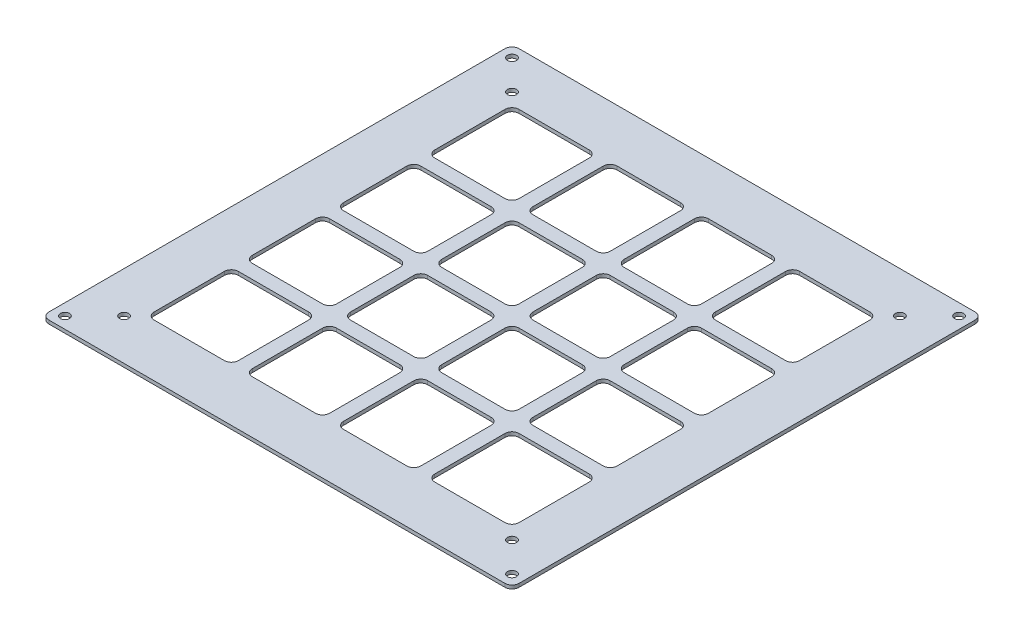
SolidWorks part; units mm, degrees
material "PC High Viscosity"
ref_plane "Front Plane" through (0, 0, 0) normal (0, 0, 1) x (1, 0, 0)
ref_plane "Top Plane" through (0, 0, 0) normal (0, 1, 0) x (1, 0, 0)
ref_plane "Right Plane" through (0, 0, 0) normal (1, 0, 0) x (0, 0, -1)
sketch "Sketch1" plane through (0, 0, 0) normal (0, 1, 0) x (1, 0, 0)
  line L0 (-101.8092, 0) -> (101.8092, 0) construction
  line L1 (-101.8092, 101.8092) -> (101.8092, 101.8092) construction
  line L2 (-101.8092, 101.8092) -> (-101.8092, -101.8092) construction
  line L3 (-101.8092, -101.8092) -> (101.8092, -101.8092) construction
  line L4 (101.8092, 101.8092) -> (101.8092, -101.8092) construction
  line L5 (-101.8092, 101.8092) -> (101.8092, -101.8092) construction
  line L6 (-101.8092, -101.8092) -> (101.8092, 101.8092) construction
  line L7 (-107.0543, 107.0543) -> (107.0543, 107.0543)
  line L8 (107.0543, 107.0543) -> (107.0543, -107.0543)
  line L9 (107.0543, -107.0543) -> (-107.0543, -107.0543)
  line L10 (-107.0543, -107.0543) -> (-107.0543, 107.0543)
  circle A0 centre (-101.8092, 101.8092) radius 2.0701
  circle A1 centre (-101.8092, -101.8092) radius 2.0701
  circle A2 centre (101.8092, -101.8092) radius 2.0701
  circle A3 centre (101.8092, 101.8092) radius 2.0701
  circle A4 centre (-88.3388, 88.3388) radius 2.0701
  circle A5 centre (88.3388, -88.3388) radius 2.0701
  circle A6 centre (88.3388, 88.3388) radius 2.0701
  circle A7 centre (-88.3388, -88.3388) radius 2.0701
  circle A8 centre (-101.8092, 101.8092) radius 5.2451 construction
  circle A9 centre (101.8092, 101.8092) radius 5.2451 construction
  circle A10 centre (101.8092, -101.8092) radius 5.2451 construction
  circle A11 centre (-101.8092, -101.8092) radius 5.2451 construction
  point P0 (0, 0)
  point P30 (0, 0)
  dimension "D2" = 4.1402
  dimension "D4" = 3.175
  dimension "D1" = 203.6183
  dimension "D3" = 19.05
  dimension "D5" = 4
extrude "Boss-Extrude1" add sketch "Sketch1" along normal blind 1.5875
sketch "Sketch2" plane through (0, 1.5875, 0) normal (0, 1, 0) x (1, 0, 0)
  line L0 (-50000, 0) -> (50000, 0) construction
  line L1 (0, 50000) -> (0, -50000) construction
  line L2 (0, 0) -> (-83.0937, 0) construction
  line L3 (0, 0) -> (0, 83.0937) construction
  line L4 (-83.0937, 83.0937) -> (-83.0937, -83.0937)
  line L5 (83.0937, 83.0937) -> (83.0937, -83.0937)
  line L6 (83.0937, -83.0937) -> (-83.0937, -83.0937)
  line L7 (-83.0937, 83.0937) -> (83.0937, 83.0937)
  line L8 (-41.5468, -83.0937) -> (-41.5468, 83.0937) construction
  line L9 (83.0937, 41.5468) -> (-83.0937, 41.5468) construction
  line L10 (83.0937, -41.5468) -> (-83.0937, -41.5468) construction
  line L11 (41.5468, -83.0937) -> (41.5468, 83.0937) construction
  line L12 (-83.0937, -3.175) -> (50000, -3.175)
  line L13 (-38.3718, -83.0937) -> (-38.3718, 83.0937)
  line L14 (83.0937, 44.7218) -> (-83.0937, 44.7218)
  line L15 (83.0937, -38.3718) -> (-83.0937, -38.3718)
  line L16 (-3.175, 83.0937) -> (-3.175, -83.0937)
  line L17 (44.7218, -83.0937) -> (44.7218, 83.0937)
  line L18 (-83.0937, 3.175) -> (50000, 3.175)
  line L19 (-44.7218, -83.0937) -> (-44.7218, 83.0937)
  line L20 (83.0937, 38.3718) -> (-83.0937, 38.3718)
  line L21 (83.0937, -44.7218) -> (-83.0937, -44.7218)
  line L22 (3.175, 83.0937) -> (3.175, -83.0937)
  line L23 (38.3718, -83.0937) -> (38.3718, 83.0937)
  line L24 (0, 44.7218) -> (-50000, 44.7218) construction
  line L25 (0, 41.5468) -> (-50000, 41.5468) construction
  line L26 (0, 38.3718) -> (-50000, 38.3718) construction
  line L27 (-50000, 3.175) -> (50000, 3.175) construction
  line L28 (-50000, -3.175) -> (50000, -3.175) construction
  line L29 (0, -38.3718) -> (-50000, -38.3718) construction
  line L30 (0, -41.5468) -> (-50000, -41.5468) construction
  line L31 (0, -44.7218) -> (-50000, -44.7218) construction
  line L32 (44.7218, 0) -> (44.7218, 50000) construction
  line L33 (41.5468, 0) -> (41.5468, 50000) construction
  line L34 (38.3718, 0) -> (38.3718, 50000) construction
  line L35 (-38.3718, 0) -> (-38.3718, 50000) construction
  line L36 (-41.5468, 0) -> (-41.5468, 50000) construction
  line L37 (-44.7218, 0) -> (-44.7218, 50000) construction
  line L38 (-3.175, 50000) -> (-3.175, -50000) construction
  line L39 (3.175, 50000) -> (3.175, -50000) construction
  circle A0 centre (-88.3388, 88.3388) radius 5.2451 construction
  circle A1 centre (-88.3388, 88.3388) radius 2.0701 construction
  circle A2 centre (88.3388, 88.3388) radius 5.2451 construction
  circle A3 centre (88.3388, -88.3388) radius 5.2451 construction
  circle A4 centre (-88.3388, -88.3388) radius 5.2451 construction
  point P19 (0, 0)
  point P22 (-41.5468, 0)
  point P27 (0, 41.5468)
  dimension "D1" = 3.175
  dimension "D3" = 3.175
  dimension "D4" = 3.175
  dimension "D2" = 4
extrude "Cut-Extrude1" cut sketch "Sketch2" against normal through all contours L14 L19 L7 L4 | L19 L20 L4 L18 | L16 L7 L13 L14 | L16 L20 L13 L18 | L14 L23 L7 L22 | L18 L23 L20 L22 | L17 L14 L5 L7 | L5 L20 L17 L18 | L17 L15 L5 L12 | L15 L23 L12 L22 | L16 L12 L13 L15 | L15 L19 L12 L4 | L19 L21 L4 L6 | L16 L21 L13 L6 | L6 L23 L21 L22 | L5 L21 L17 L6 region at (-63.9078, 1.5875, -63.9078) region at (-63.9078, 1.5875, -20.7734) region at (-20.7734, 1.5875, -63.9078) region at (-63.9078, 1.5875, 20.7734) region at (-20.7734, 1.5875, -20.7734) region at (20.7734, 1.5875, -63.9078) region at (-63.9078, 1.5875, 63.9078) region at (-20.7734, 1.5875, 20.7734) region at (20.7734, 1.5875, -20.7734) region at (63.9078, 1.5875, -63.9078) region at (-20.7734, 1.5875, 63.9078) region at (20.7734, 1.5875, 20.7734) region at (63.9078, 1.5875, -20.7734) region at (20.7734, 1.5875, 63.9078) region at (63.9078, 1.5875, 20.7734) region at (63.9078, 1.5875, 63.9078)
fillet "Fillet1" radius 3.175 4 edges at (-107.0543, 0.7937, 107.0543) (107.0543, 0.7937, 107.0543) (107.0543, 0.7937, -107.0543) (-107.0543, 0.7937, -107.0543)
fillet "Fillet2" radius 3.175 64 edges at (-38.3718, 0.7937, -44.7218) (-38.3718, 0.7937, -83.0937) (-3.175, 0.7937, -83.0937) (-3.175, 0.7937, -44.7218) (-38.3718, 0.7937, -3.175) (-38.3718, 0.7937, -38.3718) (-3.175, 0.7937, -38.3718) (-3.175, 0.7937, -3.175) (3.175, 0.7937, -83.0937) (38.3718, 0.7937, -83.0937) (38.3718, 0.7937, -44.7218) (3.175, 0.7937, -44.7218) (83.0937, 0.7937, -83.0937) (83.0937, 0.7937, -44.7218) (44.7218, 0.7937, -44.7218) (44.7218, 0.7937, -83.0937) (44.7218, 0.7937, -3.175) (44.7218, 0.7937, -38.3718) (83.0937, 0.7937, -38.3718) (83.0937, 0.7937, -3.175) (83.0937, 0.7937, 3.175) (83.0937, 0.7937, 38.3718) (44.7218, 0.7937, 38.3718) (44.7218, 0.7937, 3.175) (3.175, 0.7937, 3.175) (38.3718, 0.7937, 3.175) (38.3718, 0.7937, 38.3718) (3.175, 0.7937, 38.3718) (-38.3718, 0.7937, 38.3718) (-38.3718, 0.7937, 3.175) (-3.175, 0.7937, 3.175) (-3.175, 0.7937, 38.3718) (-83.0937, 0.7937, 3.175) (-44.7218, 0.7937, 3.175) (-44.7218, 0.7937, 38.3718) (-83.0937, 0.7937, 38.3718) (-38.3718, 0.7937, 83.0937) (-38.3718, 0.7937, 44.7218) (-3.175, 0.7937, 44.7218) (-3.175, 0.7937, 83.0937) (3.175, 0.7937, 44.7218) (38.3718, 0.7937, 44.7218) (38.3718, 0.7937, 83.0937) (3.175, 0.7937, 83.0937) (44.7218, 0.7937, 83.0937) (44.7218, 0.7937, 44.7218) (83.0937, 0.7937, 44.7218) (83.0937, 0.7937, 83.0937) (-83.0937, 0.7937, -83.0937) (-44.7218, 0.7937, -83.0937) (-44.7218, 0.7937, -44.7218) (-83.0937, 0.7937, -44.7218) (-44.7218, 0.7937, 83.0937) (-83.0937, 0.7937, 44.7218) (-44.7218, 0.7937, 44.7218) (3.175, 0.7937, -3.175) (3.175, 0.7937, -38.3718) (38.3718, 0.7937, -38.3718) (38.3718, 0.7937, -3.175) (-44.7218, 0.7937, -3.175) (-83.0937, 0.7937, -3.175) (-83.0937, 0.7937, -38.3718) (-44.7218, 0.7937, -38.3718) (-83.0937, 0.7937, 83.0937)
